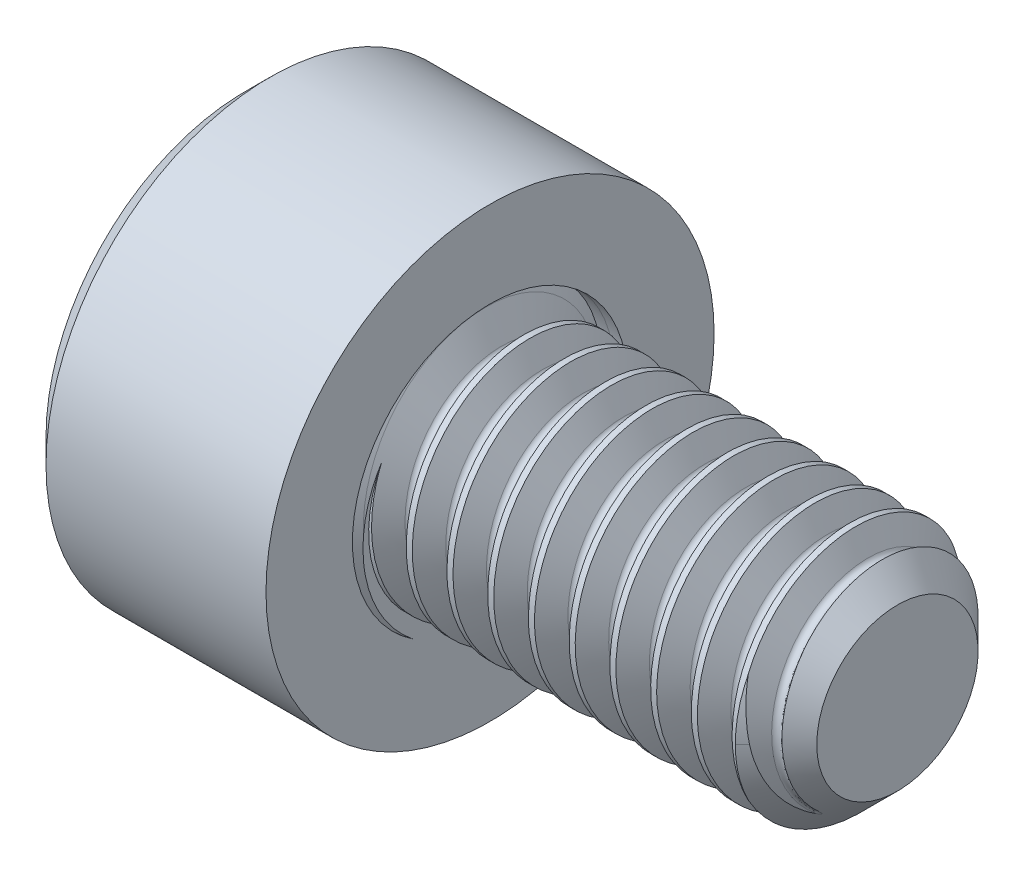
SolidWorks part; units mm, degrees
material "AISI Type 316L stainless steel"
ref_plane "Front Plane" through (0, 0, 0) normal (0, 0, 1) x (1, 0, 0)
ref_plane "Top Plane" through (0, 0, 0) normal (0, 1, 0) x (1, 0, 0)
ref_plane "Right Plane" through (0, 0, 0) normal (1, 0, 0) x (0, 0, -1)
sketch "Sketch1" plane through (0, 0, 0) normal (0, 0, 1) x (1, 0, 0)
  line L0 (-88.7055, 0) -> (96.9812, 0) construction
  line L1 (0, 0) -> (0, 2.75)
  line L2 (0, 2.75) -> (3, 2.75)
  line L4 (8, 0) -> (8, 1.49)
  line L5 (8, 1.49) -> (3, 1.49)
  line L6 (3, 1.49) -> (3, 2.75)
  line L7 (0, 0) -> (8, 0)
revolve "Revolve1" add sketch "Sketch1" angle 360 about L0
chamfer "Chamfer1" distance 0.5 angle 45 1 edges at (8, 0, 1.49)
chamfer "Chamfer2" distance 0.3 angle 45 1 edges at (0, 0, 2.75)
sketch "Sketch3" plane through (0, 0, 0) normal (1, 0, 0) x (0, 0, -1)
  line L1 (-1.4434, 0) -> (-0.7217, -1.25)
  line L2 (-0.7217, -1.25) -> (0.7217, -1.25)
  line L3 (0.7217, -1.25) -> (1.4434, 0)
  line L4 (1.4434, 0) -> (0.7217, 1.25)
  line L5 (0.7217, 1.25) -> (-0.7217, 1.25)
  line L6 (-0.7217, 1.25) -> (-1.4434, 0)
  circle A0 centre (0, 0) radius 1.25 construction
extrude "Cut-Extrude1" cut sketch "Sketch3" along normal blind 2.5
chamfer "Chamfer3" distance 0.3 angle 45 6 edges at (0, 1.25, 0) (0, 0.625, 1.0825) (0, -0.625, 1.0825) (0, -1.25, 0) (0, -0.625, -1.0825) (0, 0.625, -1.0825)
sketch "Sketch5" plane through (8, 0, 0) normal (1, 0, 0) x (0, 0, -1)
  circle A0 centre (0, 0) radius 1.5
curve "Helix/Spiral1" pitch 0.5 height 5 radius 1.5 centre (8, 0, 0) axis (-1, 0, 0) start towards (0, 0, -1)
sketch "Sketch8" plane through (0, 0, 0) normal (0, 1, 0) x (1, 0, 0)
  line L0 (8, 1.5) -> (8, 1.1211) construction
  line L1 (8.0625, 1.2294) -> (8.3281, 1.6894)
  line L2 (8.3281, 1.6894) -> (7.6719, 1.6894)
  line L3 (7.6719, 1.6894) -> (7.9375, 1.2294)
  line L4 (8, -0.99) -> (8, 0.99) construction
  circle A0 centre (8, 1.5) radius 0.1894 construction
  arc A1 (8.0625, 1.2294) -> (7.9375, 1.2294) centre (8, 1.2655) cw
  dimension "D2" = 0.0722
  dimension "D1" = 0.3789
sweep "Cut-Sweep1" cut profiles "Sketch8" path "Helix/Spiral1"
